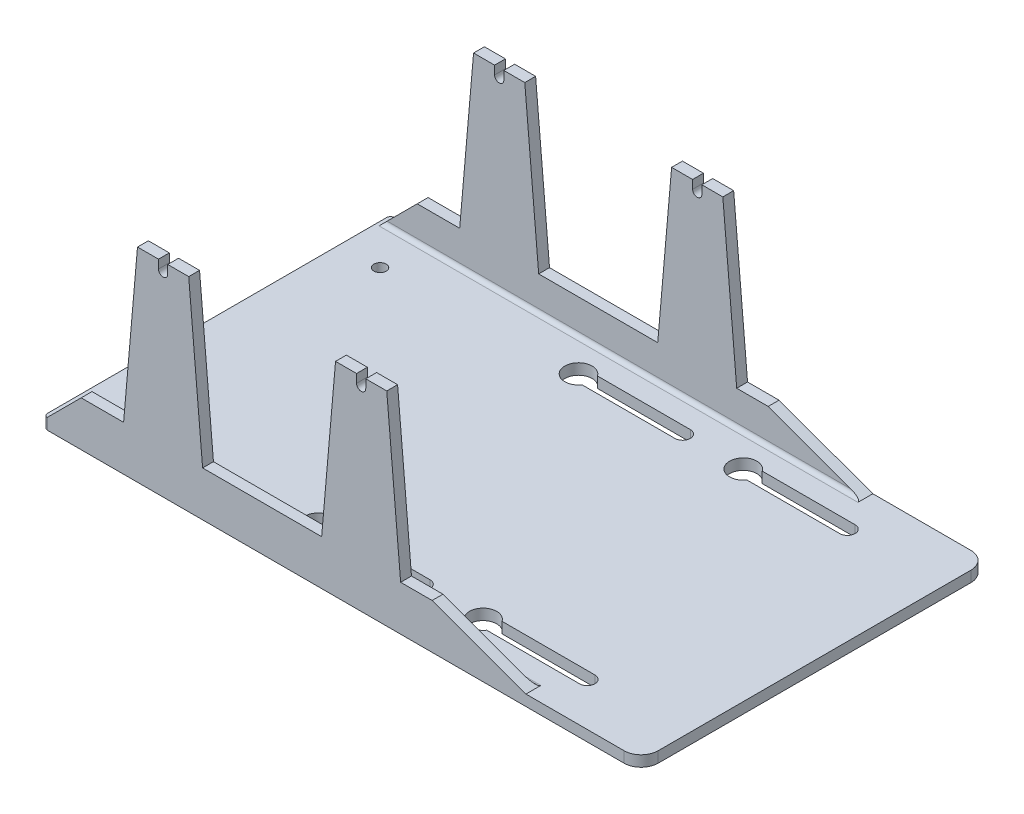
SolidWorks part; units mm, degrees
ref_plane "Front Plane" through (0, 0, 0) normal (0, 0, 1) x (1, 0, 0)
ref_plane "Top Plane" through (0, 0, 0) normal (0, 1, 0) x (1, 0, 0)
ref_plane "Right Plane" through (0, 0, 0) normal (1, 0, 0) x (0, 0, -1)
sketch "Sketch1" plane through (0, 0, 0) normal (0, 1, 0) x (1, 0, 0)
  line L0 (0, 0) -> (175, 0) construction
  line L1 (0, 50.8) -> (175, 50.8)
  line L2 (0, 50.8) -> (0, -50.8)
  line L3 (0, -50.8) -> (175, -50.8)
  line L4 (175, 50.8) -> (175, -50.8)
  line L5 (0, 50.8) -> (175, -50.8) construction
  line L6 (0, -50.8) -> (175, 50.8) construction
  point P0 (11.3289, 32.4526)
  point P5 (0, 0)
  dimension "D1" = 101.6
  dimension "D2" = 175
extrude "plate" add sketch "Sketch1" along normal blind 3.175
sketch "Sketch14" plane through (0, 0, 0) normal (0, -1, 0) x (1, 0, 0)
  text T0 "BOTTOM" font "Century Gothic" height 3.5
extrude "bottom label" cut sketch "Sketch14" against normal blind 0.6
hole_wizard "mount slots" positions "Sketch8" profile "Sketch9" size "M4" standard "ISO" slot yes end condition through all
sketch "Sketch8" plane through (0, 3.175, 0) normal (0, 1, 0) x (1, 0, 0)
  line L0 (83, 38.1) -> (131.26, 38.1) construction
  line L2 (0, 0) -> (175, 0) construction
  line L3 (175, -50.8) -> (175, 50.8) construction
  line L4 (0, 50.8) -> (0, -50.8) construction
  line L5 (83, -38.1) -> (131.26, -38.1) construction
  line L6 (65.5, 38.1) -> (100.5, 38.1) construction
  point P1 (83, 38.1)
  point P2 (131.26, 38.1)
  point P23 (131.26, -38.1)
  point P24 (83, -38.1)
  dimension "D1" = 48.26
  dimension "D2" = 38.1
  dimension "D3" = 83
  dimension "D4" = 35
sketch "Sketch9" plane through (83, 3.175, -38.1) normal (1, 0, 0) x (0, 0, 1)
  line L0 (0, 0) -> (0, 3.175)
  line L1 (0, 3.175) -> (2.25, 3.175)
  line L2 (2.25, 3.175) -> (2.25, 0)
  line L5 (2.25, 0) -> (0, 0)
  line L11 (0, -6.35) -> (0, 107.95) construction
  dimension "Thru Hole Dia." = 4.5
  dimension "Thru Hole Depth" = 3.175
sketch "Sketch12" plane through (0, 3.175, 0) normal (0, 1, 0) x (1, 0, 0)
  line L0 (-1.7462, 0) -> (1.7462, 0) construction
  circle A0 centre (116.01, 38.1) radius 4
  circle A1 centre (67.75, 38.1) radius 4
  circle A5 centre (67.75, -38.1) radius 4
  circle A6 centre (116.01, -38.1) radius 4
  arc A7 (67.75, 40.35) -> (67.75, 35.85) centre (67.75, 38.1) ccw construction
  arc A8 (116.01, 40.35) -> (116.01, 35.85) centre (116.01, 38.1) ccw construction
  dimension "D1" = 8
  dimension "D2" = 8
extrude "slot_clearance" cut sketch "Sketch12" against normal through all
hole_wizard "bracket  holes" positions "Sketch10" profile "Sketch11" hole size "M3" standard "ISO" end condition through all
sketch "Sketch10" plane through (0, 3.175, 0) normal (0, 1, 0) x (1, 0, 0)
  line L0 (0, 0) -> (175, 0) construction
  line L1 (0, 50.8) -> (0, -50.8) construction
  line L2 (175, -50.8) -> (175, 50.8) construction
  point P0 (11.75, 36)
  point P14 (11.75, -36)
  dimension "D1" = 11.75
  dimension "D2" = 36
sketch "Sketch11" plane through (11.75, 3.175, -36) normal (1, 0, 0) x (0, 0, 1)
  line L0 (0, 0) -> (0, 3.175)
  line L1 (0, 3.175) -> (1.8, 3.175)
  line L2 (1.8, 3.175) -> (1.8, 0)
  line L5 (1.8, 0) -> (0, 0)
  line L11 (0, -6.35) -> (0, 107.95) construction
  dimension "Thru Hole Dia." = 3.6
  dimension "Thru Hole Depth" = 3.175
sketch "Sketch13" plane through (0, 0, -50.8) normal (0, 0, -1) x (-1, 0, 0)
  line L0 (-141.26, 3.175) -> (-113.7852, 13.175)
  line L1 (-175, 3.175) -> (0, 3.175) construction
  line L2 (-113.7852, 13.175) -> (-11, 13.175)
  line L3 (-11, 13.175) -> (-1, 3.175)
  line L4 (-1, 3.175) -> (-141.26, 3.175)
  line L6 (0, 3.175) -> (0, 0) construction
  point P10 (0, 1.5875)
  dimension "D1" = 20
  dimension "D2" = 10
  dimension "D3" = 45
  dimension "D4" = 1
  dimension "D5" = 10
extrude "plate stiffener" add sketch "Sketch13" against normal blind 3.175
sketch "Sketch15" plane through (0, 0, -50.8) normal (0, 0, -1) x (-1, 0, 0)
  line L0 (-46.5682, 13.175) -> (-42.5, 59.675)
  line L1 (-11, 13.175) -> (-113.7852, 13.175) construction
  line L2 (-42.5, 59.675) -> (-27.5, 59.675) construction
  line L3 (-27.5, 59.675) -> (-23.4318, 13.175)
  line L4 (-35, 59.675) -> (-35, 13.175) construction
  line L5 (0, 3.175) -> (0, 0) construction
  line L6 (-46.5682, 13.175) -> (-23.4318, 13.175) construction
  line L7 (-36.35, 59.675) -> (-36.35, 57.175)
  line L8 (-33.65, 59.675) -> (-33.65, 57.175)
  line L9 (0, 3.175) -> (-175, 3.175) construction
  line L10 (-36.35, 59.675) -> (-42.5, 59.675)
  line L11 (-33.65, 59.675) -> (-27.5, 59.675)
  line L12 (-46.5682, 13.175) -> (-23.4318, 13.175)
  arc A0 (-36.35, 57.175) -> (-33.65, 57.175) centre (-35, 57.175) ccw
  point P10 (-35, 13.175)
  dimension "D3" = 2.7
  dimension "D1" = 35
  dimension "D2" = 15
  dimension "D4" = 54
  dimension "D5" = 2.5
  dimension "D6" = 85
extrude "rack ears" add sketch "Sketch15" against normal blind 3.175
pattern_linear "LPattern1" count 2 spacing 58 along (1, 0, 0) of "rack ears"
mirror "stiffener mirror" about plane through (0, 0, 0) normal (0, 0, 1) of "LPattern1", "plate stiffener"
fillet "Fillet 1.2mm" radius 1.2 4 edges at (71.13, 3.175, 47.625) (71.13, 3.175, -47.625) (0, 1.5875, -50.8) (0, 1.5875, 50.8)
fillet "Fillet2" radius 5 2 edges at (175, 1.5875, 50.8) (175, 1.5875, -50.8)
